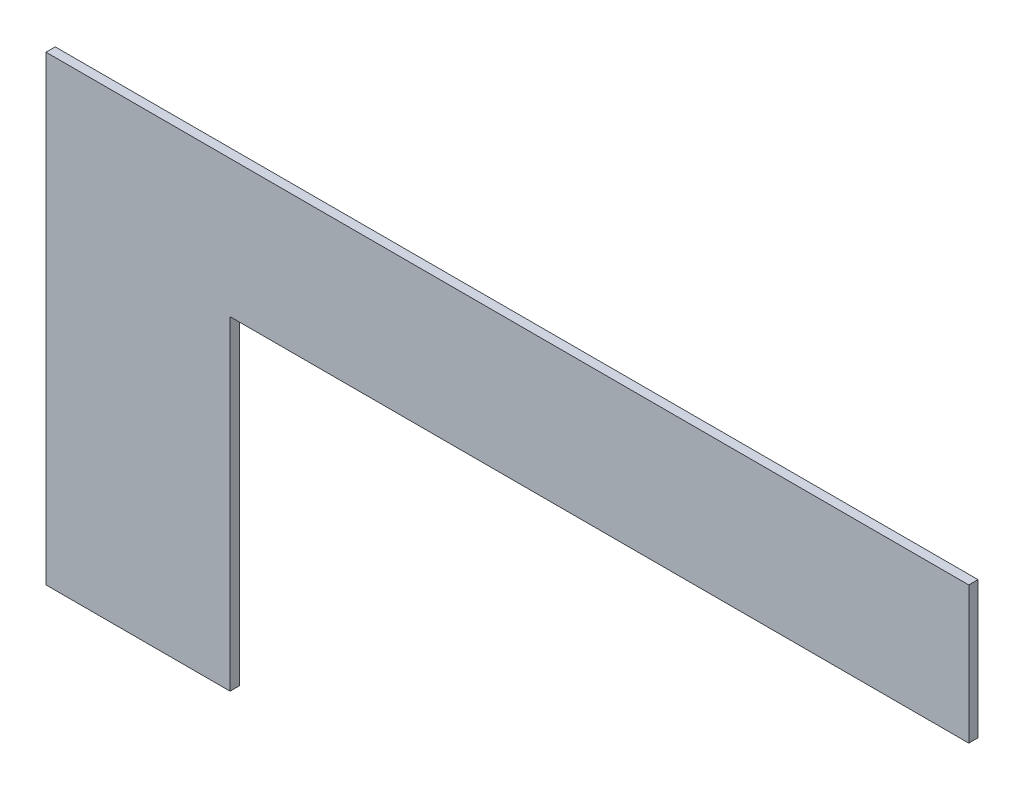
SolidWorks part; units mm, degrees
ref_plane "Ön Düzlem" through (0, 0, 0) normal (0, 0, 1) x (1, 0, 0)
ref_plane "Üst Düzlem" through (0, 0, 0) normal (0, 1, 0) x (1, 0, 0)
ref_plane "Sağ Düzlem" through (0, 0, 0) normal (1, 0, 0) x (0, 0, -1)
sketch "Çizim1" plane through (0, 0, 0) normal (0, 0, 1) x (1, 0, 0)
  line L1 (0, 0) -> (4000, 0)
  line L2 (0, 0) -> (0, -2000)
  line L3 (0, -2000) -> (800, -2000)
  line L4 (4000, 0) -> (4000, -950)
  line L7 (4000, -950) -> (800, -950)
  line L8 (800, -2000) -> (800, -950)
  dimension "D1" = 4000
  dimension "D2" = 2000
  dimension "D3" = 1050
  dimension "D4" = 3200
  dimension "D5" = 800
base flange "Taban-Flanş1" sketch "Çizim1" thickness 40 reverse thickness direction no parameters "D1"=4
sketch "Çizim2" plane through (0, 0, 0) normal (0, 0, 1) x (1, 0, 0)
  line L1 (4000, -950) -> (800, -950)
  line L2 (4000, -950) -> (4000, -600)
  line L3 (4000, -600) -> (800, -600)
  line L4 (800, -950) -> (800, -600)
  dimension "D1" = 350
  dimension "D2" = 3200
extrude "Kes-Ekstrüzyon1" cut sketch "Çizim2" against normal through all both and the other way through all
sketch "Çizim3" plane through (0, 0, 0) normal (0, 0, 1) x (1, 0, 0)
  line L0 (4000, -600) -> (4000, 0) construction
  line L1 (800, -600) -> (4000, -600)
  line L2 (800, -600) -> (800, -594)
  line L3 (800, -594) -> (4000, -594)
  line L4 (4000, -600) -> (4000, -594)
  line L5 (4000, 0) -> (0, 0) construction
  dimension "D1" = 594
extrude "Kes-Ekstrüzyon2" cut sketch "Çizim3" against normal through all both and the other way through all
sketch "Çizim4" plane through (0, 0, 0) normal (0, 0, 1) x (1, 0, 0)
  line L0 (4000, -594) -> (800, -594) construction
  line L1 (800, -2000) -> (798, -2000)
  line L2 (800, -2000) -> (800, -594)
  line L3 (800, -594) -> (798, -594)
  line L4 (798, -2000) -> (798, -594)
  line L5 (0, 0) -> (0, -2000) construction
  dimension "D1" = 798
extrude "Kes-Ekstrüzyon3" cut sketch "Çizim4" against normal through all both and the other way through all
sketch "Çizim5" plane through (0, 0, 0) normal (0, 0, 1) x (1, 0, 0)
  line L6 (798, -2000) -> (798, -594)
  line L7 (798, -594) -> (4000, -594)
  line L8 (4000, -594) -> (4000, 0)
  line L9 (4000, 0) -> (0, 0)
  line L10 (0, 0) -> (0, -2000)
  line L11 (0, -2000) -> (798, -2000)
  line L12 (798, -2000) -> (798, -594)
  line L13 (798, -594) -> (4000, -594)
  line L14 (4000, -594) -> (4000, 0)
  line L15 (4000, 0) -> (0, 0)
  line L16 (0, 0) -> (0, -2000)
  line L17 (0, -2000) -> (798, -2000)
  dimension "D2" = 4000
  dimension "D3" = 594
  dimension "D4" = 3202
  dimension "D5" = 1406
  dimension "D6" = 798
  dimension "D7" = 2000
  dimension "D1" = 0
sketch "Büküm-Çizgileri1" [suppressed] plane through (0, 0, 0) normal (0, 1, 0) x (1, 0, 0)
sketch "Sınırlandırma-Kutusu1" [suppressed] plane through (0, 0, 0) normal (0, 1, 0) x (1, 0, 0)
sheet metal parameters "Sac-Levha1" thickness 40 parameters "D1"=4
flat pattern "Düz-Çoğaltma1" [suppressed]
sketch "Büküm-Çizgileri2" plane through (0, 0, 0) normal (0, 1, 0) x (1, 0, 0)
sketch3d "Sınırlandırma-Kutusu2" [suppressed]
  line L0 (0, -2000, 0) -> (4000, -2000, 0) construction
  line L1 (0, 0, 0) -> (4000, 0, 0) construction
  line L2 (0, -2000, 0) -> (0, 0, 0) construction
  line L3 (4000, -2000, 0) -> (4000, 0, 0) construction
sheet metal parameters "Sac-Levha2" thickness 40 parameters "D1"=4
flat pattern "Düz-Çoğaltma1"
sketch "Büküm-Çizgileri2" plane through (0, 0, 0) normal (0, 1, 0) x (1, 0, 0)
sketch3d "Sınırlandırma-Kutusu2" [suppressed]
  line L0 (0, -2000, 0) -> (4000, -2000, 0) construction
  line L1 (0, 0, 0) -> (4000, 0, 0) construction
  line L2 (0, -2000, 0) -> (0, 0, 0) construction
  line L3 (4000, -2000, 0) -> (4000, 0, 0) construction
sheet metal parameters "Sac-Levha3" thickness 40 parameters "D1"=4
flat pattern "Düz-Çoğaltma1"
sketch "Büküm-Çizgileri2" plane through (0, 0, 0) normal (0, 1, 0) x (1, 0, 0)
sketch3d "Sınırlandırma-Kutusu2" [suppressed]
  line L0 (0, -2000, 0) -> (4000, -2000, 0) construction
  line L1 (0, 0, 0) -> (4000, 0, 0) construction
  line L2 (0, -2000, 0) -> (0, 0, 0) construction
  line L3 (4000, -2000, 0) -> (4000, 0, 0) construction
sheet metal parameters "Sac-Levha4" thickness 40 parameters "D1"=4
flat pattern "Düz-Çoğaltma1"
sketch "Büküm-Çizgileri2" plane through (0, 0, 0) normal (0, 1, 0) x (1, 0, 0)
sketch3d "Sınırlandırma-Kutusu2" [suppressed]
  line L0 (0, -2000, 0) -> (4000, -2000, 0) construction
  line L1 (0, 0, 0) -> (4000, 0, 0) construction
  line L2 (0, -2000, 0) -> (0, 0, 0) construction
  line L3 (4000, -2000, 0) -> (4000, 0, 0) construction
